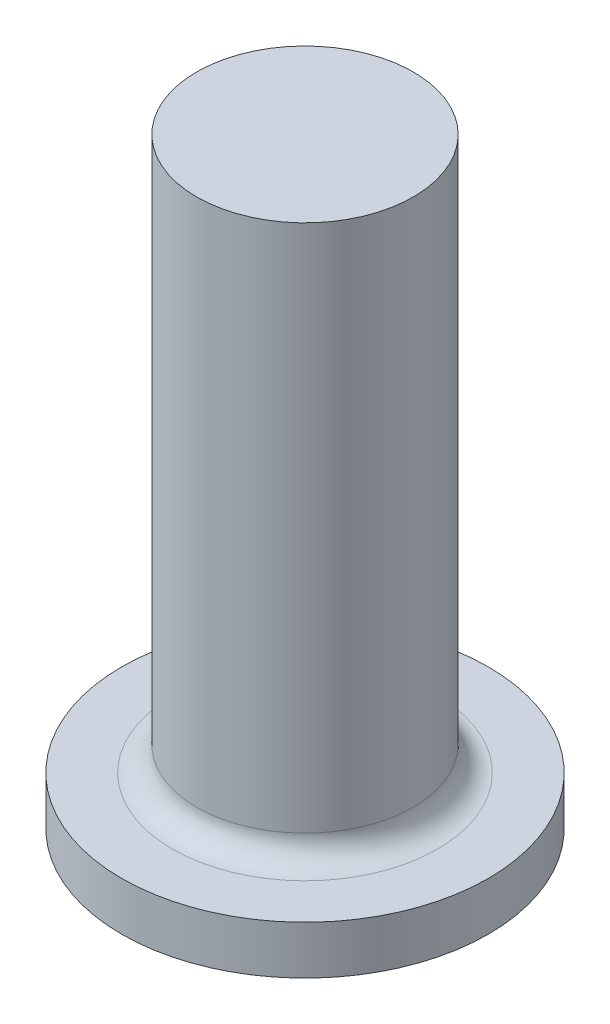
SolidWorks part; units mm, degrees
ref_plane "Front Plane" through (0, 0, 0) normal (0, 0, 1) x (1, 0, 0)
ref_plane "Top Plane" through (0, 0, 0) normal (0, 1, 0) x (1, 0, 0)
ref_plane "Right Plane" through (0, 0, 0) normal (1, 0, 0) x (0, 0, -1)
sketch "Sketch1" plane through (0, 0, 0) normal (0, 1, 0) x (1, 0, 0)
  circle A0 centre (0, 0) radius 37.9
extrude "Boss-Extrude1" add sketch "Sketch1" along normal blind 10
sketch "Sketch2" plane through (0, 10, 0) normal (0, 1, 0) x (1, 0, 0)
  circle A0 centre (0, 0) radius 22.4
extrude "Boss-Extrude2" add sketch "Sketch2" along normal blind 114.3
fillet "Fillet1" radius 5 1 edges at (0, 10, 22.4)
